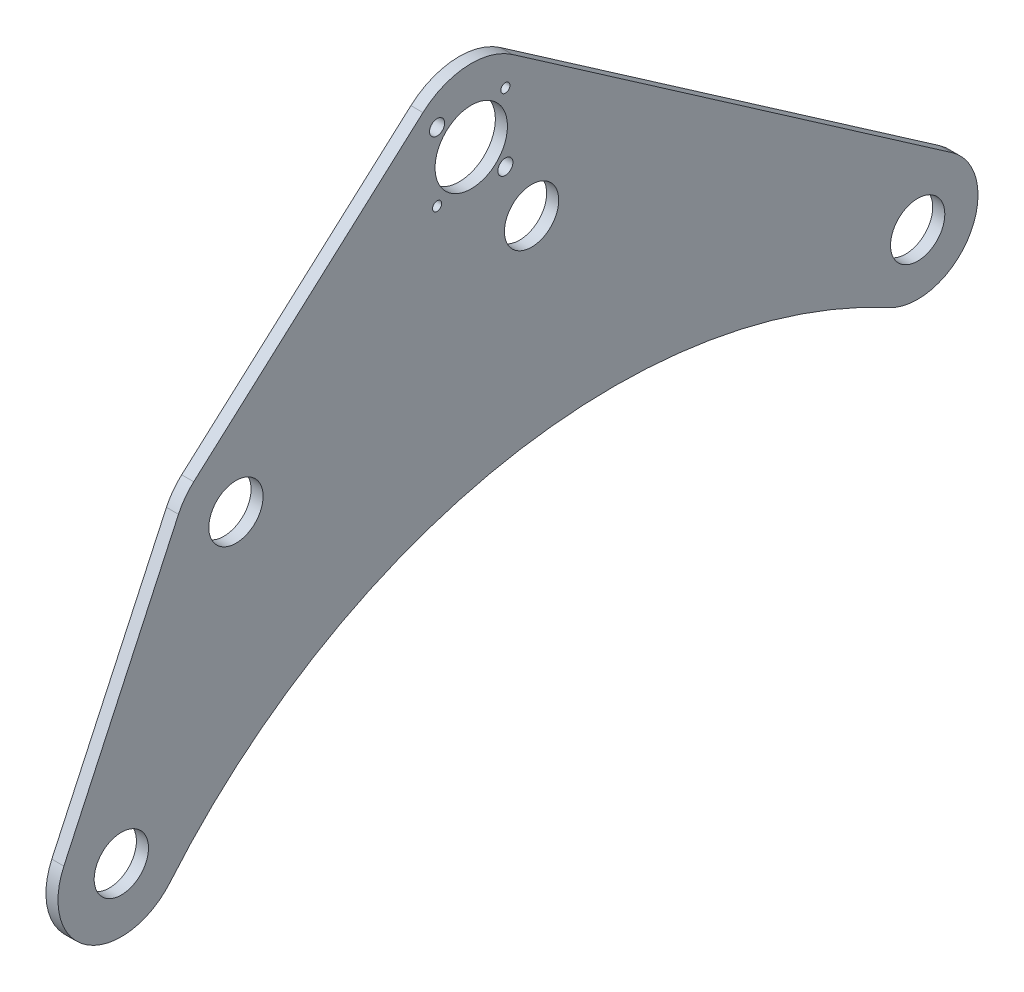
SolidWorks part; units mm, degrees
material "Acrylic (Medium-high impact)"
ref_plane "Front Plane" through (0, 0, 0) normal (0, 0, 1) x (1, 0, 0)
ref_plane "Top Plane" through (0, 0, 0) normal (0, 1, 0) x (1, 0, 0)
ref_plane "Right Plane" through (0, 0, 0) normal (1, 0, 0) x (0, 0, -1)
sketch "Sketch1" plane through (0, 0, 0) normal (1, 0, 0) x (0, 0, -1)
  line L0 (-548.7618, -304.8) -> (152.435, -304.8)
  line L1 (-192.8252, -120.65) -> (-152.4, -120.65)
  line L2 (-234.95, -162.7748) -> (-234.95, -205.5252)
  line L3 (-192.8252, -247.65) -> (-152.4, -247.65)
  line L4 (-152.4, -120.65) -> (-152.4, -247.65)
  circle A1 centre (0, 0) radius 6.35
  circle A6 centre (-419.1, -79.375) radius 9.525
  circle A7 centre (-358.775, 50.8) radius 9.525
  circle A8 centre (-203.2, 107.95) radius 9.525
  arc A9 (-234.95, -205.5252) -> (-192.8252, -247.65) centre (-192.8252, -205.5252) ccw
  arc A10 (-192.8252, -120.65) -> (-234.95, -162.7748) centre (-192.8252, -162.7748) ccw
  circle A11 centre (-358.775, -182.7754) radius 120.65
  circle A12 centre (-234.95, 155.194) radius 29.845
  dimension "D1" = 12.7
  dimension "D2" = 19.05
  dimension "D3" = 42.1248
  dimension "D4" = 127
  dimension "D7" = 184.15
  dimension "D6" = 241.3
  dimension "D16" = 59.69
  dimension "D5" = 82.55
  dimension "D8" = 304.8
  dimension "D9" = 152.4
  dimension "D10" = 419.1
  dimension "D11" = 79.375
  dimension "D12" = 358.775
  dimension "D13" = 50.8
  dimension "D14" = 203.2
  dimension "D15" = 107.95
  dimension "D17" = 234.95
  dimension "D18" = 155.194
sketch "Sketch2" plane through (0, 0, 0) normal (1, 0, 0) x (0, 0, -1)
  line L1 (-449.3475, -65.3579) -> (-389.0225, 64.8171)
  line L3 (-381.0036, 75.6451) -> (-260.3541, 183.5884)
  line L5 (-213.2394, 186.5031) -> (18.0922, 26.0909)
  arc A0 (-381.0036, 75.6451) -> (-389.0225, 64.8171) centre (-358.775, 50.8) ccw
  arc A2 (-449.3475, -65.3579) -> (-393.5233, -100.7578) centre (-419.1, -79.375) ccw
  arc A4 (-213.2394, 186.5031) -> (-260.3541, 183.5884) centre (-234.95, 155.194) ccw
  arc A5 (-15.0641, -27.9488) -> (18.0922, 26.0909) centre (0, 0) ccw
  arc A8 (-393.5233, -100.7578) -> (-15.0641, -27.9488) centre (-159.6794, -296.2573) cw
  circle A12 centre (-419.1, -79.375) radius 9.525 construction
  circle A13 centre (-358.775, 50.8) radius 9.525 construction
  dimension "D1" = 33.3375
  dimension "D2" = 63.5
  dimension "D3" = 76.2
  dimension "D4" = 304.8
extrude "Boss-Extrude1" add sketch "Sketch2" along normal blind 6.35
sketch "Sketch3" plane through (6.35, 0, 0) normal (1, 0, 0) x (0, 0, -1)
  line L0 (-216.9895, 173.1545) -> (-252.9105, 137.2335) construction
  line L1 (-234.95, 155.194) -> (-234.95, 205.0182) construction
  line L2 (-252.9105, 173.1545) -> (-216.9895, 137.2335) construction
  circle A0 centre (-203.2, 107.95) radius 14.2875
  circle A1 centre (-358.775, 50.8) radius 14.2875
  circle A2 centre (-419.1, -79.375) radius 14.2875
  circle A3 centre (-234.95, 155.194) radius 19.05
  circle A4 centre (0, 0) radius 14.2875
  circle A5 centre (-252.9105, 137.2335) radius 2.413
  circle A7 centre (-216.9895, 137.2335) radius 3.9687
  circle A8 centre (-216.9895, 173.1545) radius 2.413
  circle A9 centre (-252.9105, 173.1545) radius 3.9687
  point P18 (-234.95, 155.194)
  point P25 (0, 0)
  point P28 (-234.95, 155.194)
  point P29 (0, 0)
  dimension "D1" = 38.1
  dimension "D2" = 28.575
  dimension "D3" = 4.826
  dimension "D4" = 50.8
  dimension "D5" = 45
  dimension "D6" = 7.9375
  dimension "D7" = 50.8
extrude "Cut-Extrude1" cut sketch "Sketch3" against normal up to next
